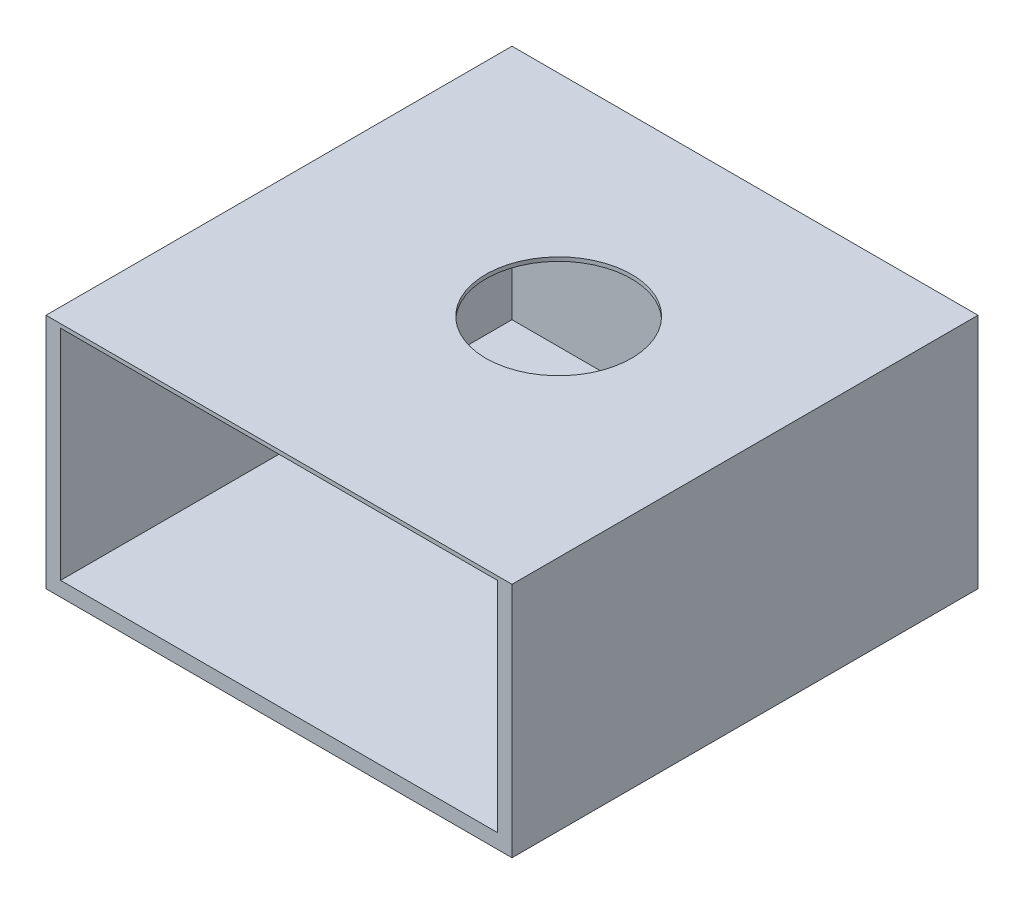
SolidWorks part; units mm, degrees
ref_plane "Front Plane" through (0, 0, 0) normal (0, 0, 1) x (1, 0, 0)
ref_plane "Top Plane" through (0, 0, 0) normal (0, 1, 0) x (1, 0, 0)
ref_plane "Right Plane" through (0, 0, 0) normal (1, 0, 0) x (0, 0, -1)
sketch "Sketch1" plane through (0, 0, 0) normal (0, 0, 1) x (1, 0, 0)
  line L1 (-152.4, -76.2) -> (152.4, -76.2)
  line L2 (-152.4, -76.2) -> (-152.4, 76.2)
  line L3 (-152.4, 76.2) -> (152.4, 76.2)
  line L4 (152.4, -76.2) -> (152.4, 76.2)
  line L5 (-152.4, -76.2) -> (152.4, 76.2) construction
  line L6 (-152.4, 76.2) -> (152.4, -76.2) construction
  point P0 (0, 0)
  dimension "D1" = 304.8
  dimension "D2" = 152.4
extrude "Boss-Extrude1" add sketch "Sketch1" along normal blind 304.8
shell "Shell1" thickness 9.525 removed face at (0, 0, 304.8) removed face at (0, 76.2, 152.4)
sketch "Sketch2" plane through (0, 76.2, 0) normal (0, 1, 0) x (1, 0, 0)
  line L0 (-142.875, -304.8) -> (142.875, -304.8)
  line L8 (-152.4, -304.8) -> (-142.875, -304.8)
  line L9 (-142.875, -304.8) -> (-142.875, -9.525)
  line L10 (-142.875, -9.525) -> (142.875, -9.525)
  line L11 (142.875, -9.525) -> (142.875, -304.8)
  line L12 (142.875, -304.8) -> (152.4, -304.8)
  line L13 (152.4, -304.8) -> (152.4, 0)
  line L14 (152.4, 0) -> (-152.4, 0)
  line L15 (-152.4, 0) -> (-152.4, -304.8)
  line L16 (-152.4, -304.8) -> (-142.875, -304.8)
  line L20 (142.875, -304.8) -> (152.4, -304.8)
  line L21 (152.4, -304.8) -> (152.4, 0)
  line L22 (152.4, 0) -> (-152.4, 0)
  line L23 (-152.4, 0) -> (-152.4, -304.8)
  dimension "D1" = 0
extrude "Boss-Extrude2" add sketch "Sketch2" along normal blind 2.54
sketch "Sketch3" plane through (0, 78.74, 0) normal (0, 1, 0) x (1, 0, 0)
  line L10 (15.875, -108.3347) -> (-28.9142, -140.876)
  line L11 (-28.9142, -140.876) -> (-11.8063, -193.5289)
  line L12 (-11.8063, -193.5289) -> (43.5563, -193.5289)
  line L13 (43.5563, -193.5289) -> (60.6642, -140.876)
  line L14 (60.6642, -140.876) -> (15.875, -108.3347)
  circle A1 centre (15.875, -155.4289) radius 3.175
sketch "Sketch4" plane through (0, 78.74, 0) normal (0, 1, 0) x (1, 0, 0)
  circle A1 centre (15.875, -137.7401) radius 47.625
  dimension "D1" = 95.25
extrude "Cut-Extrude1" cut sketch "Sketch4" against normal blind 7.62
sketch "Sketch5" plane through (0, 78.74, 0) normal (0, 1, 0) x (1, 0, 0)
  line L2 (89.7396, -162.406) -> (138.9776, -162.406)
  line L3 (138.9776, -156.056) -> (89.7396, -156.056)
  ellipse E1 centre (138.9776, -159.231) end of major axis (138.9776, -156.056) minor radius 3.0047
sketch "Sketch6" plane through (0, 78.74, 0) normal (0, 1, 0) x (1, 0, 0)
  line L0 (138.9776, -159.231) -> (95.0898, -159.231) construction
  line L1 (138.9776, -163.5234) -> (95.0898, -163.5234)
  line L2 (138.9776, -154.9386) -> (95.0898, -154.9386)
  arc A0 (138.9776, -163.5234) -> (138.9776, -154.9386) centre (138.9776, -159.231) ccw
  arc A1 (95.0898, -154.9386) -> (95.0898, -163.5234) centre (95.0898, -159.231) ccw
  point P3 (117.0337, -159.231)
extrude "Cut-Extrude2" [suppressed] cut sketch "Sketch6" against normal blind 2.54
sketch "Sketch8" plane through (0, 78.74, 0) normal (0, 1, 0) x (1, 0, 0)
  line L1 (138.4375, -185.3651) -> (89.5629, -185.3651)
  line L4 (-152.4, 0) -> (-152.4, -304.8)
  line L5 (-152.4, -304.8) -> (152.4, -304.8)
  line L6 (152.4, -304.8) -> (152.4, 0)
  line L7 (152.4, 0) -> (-152.4, 0)
  line L8 (-152.4, 0) -> (-152.4, -304.8)
  line L9 (-152.4, -304.8) -> (152.4, -304.8)
  line L10 (152.4, -304.8) -> (152.4, 0)
  line L11 (152.4, 0) -> (-152.4, 0)
  ellipse E2 centre (138.4375, -188.5401) end of major axis (138.4375, -185.3651) minor radius 3.0073
  dimension "D1" = 0
sketch "Sketch9" plane through (0, 78.74, 0) normal (0, 1, 0) x (1, 0, 0)
  line L0 (138.4375, -188.5401) -> (91.5808, -188.5401) construction
  line L1 (138.4375, -194.05) -> (91.5808, -194.05)
  line L2 (138.4375, -183.0302) -> (91.5808, -183.0302)
  arc A0 (138.4375, -194.05) -> (138.4375, -183.0302) centre (138.4375, -188.5401) ccw
  arc A1 (91.5808, -183.0302) -> (91.5808, -194.05) centre (91.5808, -188.5401) ccw
  point P3 (115.0091, -188.5401)
